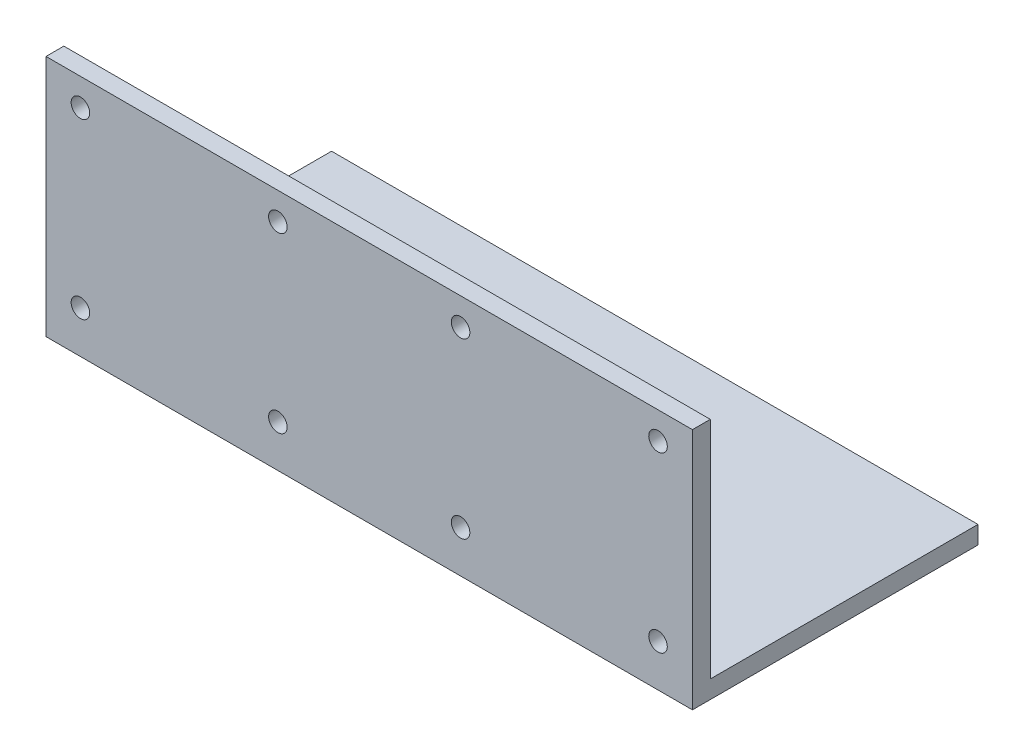
SolidWorks part; units mm, degrees
ref_plane "Front Plane" through (0, 0, 0) normal (0, 0, 1) x (1, 0, 0)
ref_plane "Top Plane" through (0, 0, 0) normal (0, 1, 0) x (1, 0, 0)
ref_plane "Right Plane" through (0, 0, 0) normal (1, 0, 0) x (0, 0, -1)
sketch "Sketch1" plane through (0, 0, 0) normal (1, 0, 0) x (0, 0, -1)
  line L0 (-44.45, 3.175) -> (-50.8, 3.175) construction
  line L1 (-50.8, -3.175) -> (50.8, -3.175)
  line L2 (-50.8, -3.175) -> (-50.8, 3.175)
  line L3 (-44.45, 3.175) -> (50.8, 3.175)
  line L4 (50.8, -3.175) -> (50.8, 3.175)
  line L5 (-50.8, -3.175) -> (50.8, 3.175) construction
  line L6 (-50.8, 3.175) -> (50.8, -3.175) construction
  line L8 (-50.8, 3.175) -> (-50.8, 83.175)
  line L9 (-50.8, 83.175) -> (-44.45, 83.175)
  line L10 (-44.45, 3.175) -> (-44.45, 83.175)
  line L11 (-50.8, 3.175) -> (-44.45, 83.175) construction
  line L12 (-50.8, 83.175) -> (-44.45, 3.175) construction
  point P0 (0, 0)
  point P6 (-47.625, 43.175)
  dimension "D1" = 6.35
  dimension "D2" = 101.6
  dimension "D3" = 80
extrude "Boss-Extrude1" add sketch "Sketch1" along normal mid plane 230
sketch "Sketch2" plane through (0, 0, 44.45) normal (0, 0, -1) x (-1, 0, 0)
  circle A0 centre (-32.5, 73.4917) radius 3.3
  circle A1 centre (-32.5, 11.825) radius 3.3
  circle A2 centre (32.5, 11.825) radius 3.3
  circle A3 centre (32.5, 73.4917) radius 3.3
  circle A6 centre (-102.75, 73.4917) radius 3.3
  circle A7 centre (-102.75, 11.825) radius 3.3
  circle A8 centre (102.75, 73.4917) radius 3.3
  circle A9 centre (102.75, 11.825) radius 3.3
  dimension "D1" = 6.6
extrude "Cut-Extrude1" cut sketch "Sketch2" against normal through all
equation "\"M5_Thread\"= 4.2mm"
equation "\"M5_Pass\"= 5.5"
equation "\"M6_Thread\"= 5mm"
equation "\"M6_Pass\"= 6.6"
equation "\"M5_Head\"= 9mm"
equation "\"M6_Head\"= 10.5"
equation "\"M5_HeadDepth\"= 5.5"
equation "\"M6_HeadDepth\"= 5.9 + .5"
